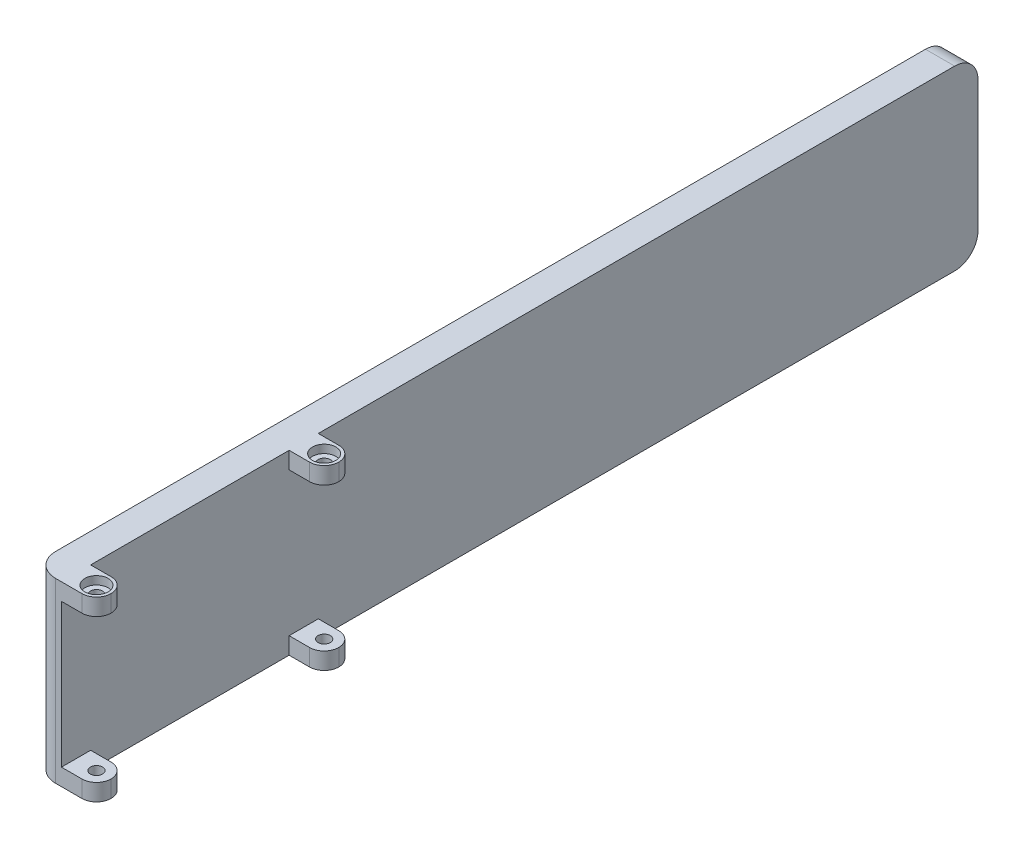
SolidWorks part; units mm, degrees
material "Esun Hard Tough Resin"
ref_plane "Front Plane" through (0, 0, 0) normal (0, 0, 1) x (1, 0, 0)
ref_plane "Top Plane" through (0, 0, 0) normal (0, 1, 0) x (1, 0, 0)
ref_plane "Right Plane" through (0, 0, 0) normal (1, 0, 0) x (0, 0, -1)
sketch "Sketch1" plane through (0, 0, 0) normal (0, 1, 0) x (1, 0, 0)
  line L1 (0, 0) -> (-5, 0)
  line L2 (0, 0) -> (0, 157)
  line L3 (0, 157) -> (-5, 157)
  line L4 (-5, 0) -> (-5, 157)
  dimension "D1" = 5
  dimension "D2" = 157
extrude "Boss-Extrude1" add sketch "Sketch1" along normal blind 30.4
sketch "Sketch2" plane through (0, 0, 0) normal (1, 0, 0) x (0, 0, -1)
  line L0 (0, 30.4) -> (157, 30.4) construction
  line L1 (0, 30.4) -> (5, 30.4)
  line L2 (0, 30.4) -> (0, 27.5)
  line L3 (0, 27.5) -> (5, 27.5)
  line L4 (5, 30.4) -> (5, 27.5)
  line L5 (39, 30.4) -> (44, 30.4)
  line L6 (39, 30.4) -> (39, 27.5)
  line L7 (39, 27.5) -> (44, 27.5)
  line L8 (44, 30.4) -> (44, 27.5)
  line L9 (-1000, 15.2) -> (49000, 15.2) construction
  line L10 (0, 30.4) -> (0, 0) construction
  line L11 (39, 2.9) -> (44, 2.9)
  line L12 (44, 0) -> (44, 2.9)
  line L13 (39, 0) -> (44, 0)
  line L14 (39, 0) -> (39, 2.9)
  line L15 (0, 2.9) -> (5, 2.9)
  line L16 (5, 0) -> (5, 2.9)
  line L17 (0, 0) -> (5, 0)
  line L18 (0, 0) -> (0, 2.9)
  point P12 (2.5, 27.5)
  point P16 (0, 15.2)
  point P17 (41.5, 27.5)
  dimension "D1" = 39
  dimension "D2" = 5
  dimension "D3" = 2.9
extrude "Boss-Extrude2" add sketch "Sketch2" along normal blind 6
sketch "Sketch3" plane through (0, 30.4, 0) normal (0, 1, 0) x (1, 0, 0)
  line L0 (6, 44) -> (6, 39) construction
  line L1 (6, 44) -> (6, 39) construction
  circle A0 centre (3.5, 41.5) radius 1.05
  circle A1 centre (3.5, 2.5) radius 1.05
  point P8 (6, 41.5)
  dimension "D1" = 2.1
  dimension "D2" = 39
  dimension "D3" = 2.5
extrude "Cut-Extrude1" cut sketch "Sketch3" against normal through all
sketch "Sketch4" plane through (0, 30.4, 0) normal (0, 1, 0) x (1, 0, 0)
  circle A0 centre (3.5, 2.5) radius 1.05 construction
  circle A1 centre (3.5, 41.5) radius 1.05 construction
  circle A2 centre (3.5, 2.5) radius 1.05 construction
  circle A3 centre (3.5, 41.5) radius 1.05 construction
  circle A4 centre (3.5, 41.5) radius 2
  circle A5 centre (3.5, 2.5) radius 2
  dimension "D1" = 4
extrude "Cut-Extrude2" cut sketch "Sketch4" against normal blind 1.4
ref_plane "Plane1" through (0, 15.2, 0) normal (0, 1, 0) x (1, 0, 0)
mirror "Mirror2" about plane through (0, 15.2, 0) normal (0, 1, 0) of "Cut-Extrude2"
fillet "Fillet1" radius 4 3 edges at (-2.5, 0, -157) (-2.5, 30.4, -157) (-5, 15.2, 0)
fillet "Fillet2" radius 2.5 8 edges at (6, 1.45, -5) (6, 1.45, 0) (6, 1.45, -44) (6, 1.45, -39) (6, 28.95, -44) (6, 28.95, -39) (6, 28.95, -5) (6, 28.95, 0)
